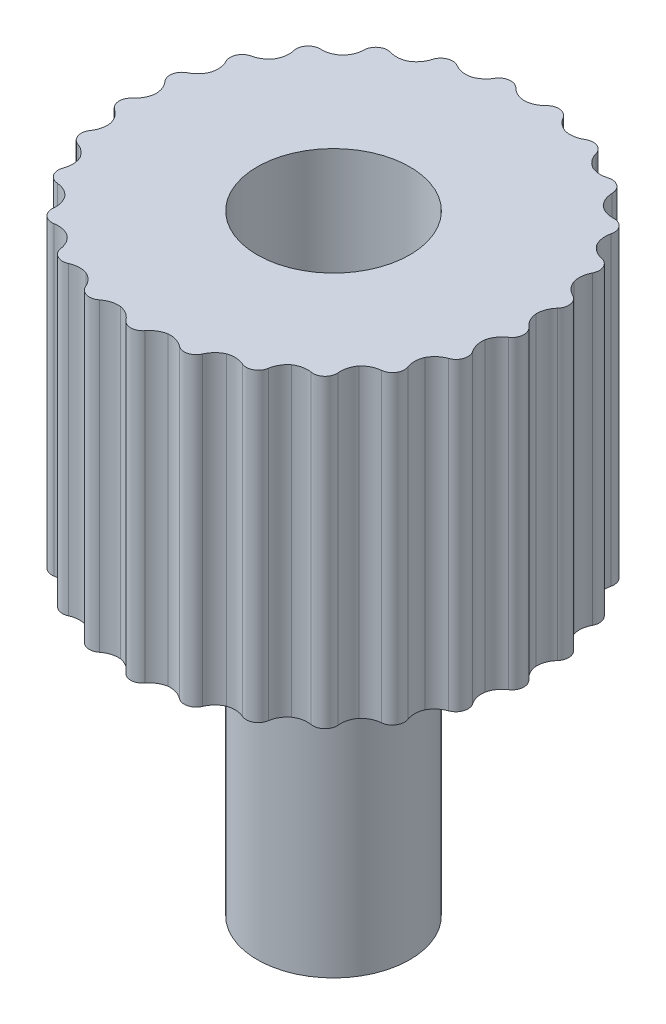
SolidWorks part; units mm, degrees
ref_plane "Front Plane" through (0, 0, 0) normal (0, 0, 1) x (1, 0, 0)
ref_plane "Top Plane" through (0, 0, 0) normal (0, 1, 0) x (1, 0, 0)
ref_plane "Right Plane" through (0, 0, 0) normal (1, 0, 0) x (0, 0, -1)
sketch "Sketch1" plane through (0, 0, 0) normal (0, 1, 0) x (1, 0, 0)
  circle A0 centre (0, 0) radius 2.5
  arc A1 (-0.157, -2.4951) -> (0.157, -2.4951) centre (0, -2.5) ccw
  arc A2 (-0.7725, -2.3776) -> (-0.4685, -2.4557) centre (-0.6217, -2.4215) ccw
  arc A3 (-1.3396, -2.1108) -> (-1.0644, -2.2621) centre (-1.2044, -2.1908) ccw
  arc A4 (-1.8224, -1.7114) -> (-1.5936, -1.9263) centre (-1.7114, -1.8224) ccw
  arc A5 (-2.1908, -1.2044) -> (-2.0225, -1.4695) centre (-2.1108, -1.3396) ccw
  arc A6 (-2.4215, -0.6217) -> (-2.3244, -0.9203) centre (-2.3776, -0.7725) ccw
  arc A7 (-2.5, 0) -> (-2.4803, -0.3133) centre (-2.4951, -0.157) ccw
  arc A8 (-2.4215, 0.6217) -> (-2.4803, 0.3133) centre (-2.4557, 0.4685) ccw
  arc A9 (-2.1908, 1.2044) -> (-2.3244, 0.9203) centre (-2.2621, 1.0644) ccw
  arc A10 (-1.8224, 1.7114) -> (-2.0225, 1.4695) centre (-1.9263, 1.5936) ccw
  arc A11 (-1.3396, 2.1108) -> (-1.5936, 1.9263) centre (-1.4695, 2.0225) ccw
  arc A12 (-0.7725, 2.3776) -> (-1.0644, 2.2621) centre (-0.9203, 2.3244) ccw
  arc A13 (-0.157, 2.4951) -> (-0.4685, 2.4557) centre (-0.3133, 2.4803) ccw
  arc A14 (0.4685, 2.4557) -> (0.157, 2.4951) centre (0.3133, 2.4803) ccw
  arc A15 (1.0644, 2.2621) -> (0.7725, 2.3776) centre (0.9203, 2.3244) ccw
  arc A16 (1.5936, 1.9263) -> (1.3396, 2.1108) centre (1.4695, 2.0225) ccw
  arc A17 (2.0225, 1.4695) -> (1.8224, 1.7114) centre (1.9263, 1.5936) ccw
  arc A18 (2.3244, 0.9203) -> (2.1908, 1.2044) centre (2.2621, 1.0644) ccw
  arc A19 (2.4803, 0.3133) -> (2.4215, 0.6217) centre (2.4557, 0.4685) ccw
  arc A20 (2.4803, -0.3133) -> (2.5, 0) centre (2.4951, -0.157) ccw
  arc A21 (2.3244, -0.9203) -> (2.4215, -0.6217) centre (2.3776, -0.7725) ccw
  arc A22 (2.0225, -1.4695) -> (2.1908, -1.2044) centre (2.1108, -1.3396) ccw
  arc A23 (1.5936, -1.9263) -> (1.8224, -1.7114) centre (1.7114, -1.8224) ccw
  arc A24 (1.0644, -2.2621) -> (1.3396, -2.1108) centre (1.2044, -2.1908) ccw
  arc A25 (0.4685, -2.4557) -> (0.7725, -2.3776) centre (0.6217, -2.4215) ccw
  circle A26 centre (0, 0) radius 1
  point P78 (0, 0)
  point P82 (0, 0)
  dimension "D1" = 5
  dimension "D2" = 7.2
  dimension "D3" = 25
extrude "Boss-Extrude1" add sketch "Sketch1" along normal blind 4 contours A0 | A0 A2 | A0 A3 | A0 A4 | A0 A5 | A0 A6 | A0 A7 | A0 A8 | A0 A9 | A0 A10 | A0 A11 | A0 A12 | A0 A13 | A0 A14 | A0 A15 | A0 A16 | A0 A17 | A0 A18 | A0 A19 | A0 A20 | A0 A21 | A0 A22 | A0 A23 | A0 A24 | A0 A25 | A0 A1 region at (2.4245, 0, 0.1525) region at (2.5607, 0, 0.1611) region at (2.5203, 0, -0.4808) region at (2.4402, 0, 0.7929) region at (2.3216, 0, -1.0924) region at (2.1663, 0, 1.3748) region at (1.977, 0, -1.6355) region at (1.7564, 0, 1.8704) region at (1.5081, 0, -2.0757) region at (1.2361, 0, 2.2484) region at (0.9445, 0, -2.3856) region at (0.6381, 0, 2.4852) region at (0.3216, 0, -2.5455) region at (0, 0, 2.5658) region at (-0.3216, 0, -2.5455) region at (-0.6381, 0, 2.4852) region at (-0.9445, 0, -2.3856) region at (-1.2361, 0, 2.2484) region at (-1.5081, 0, -2.0757) region at (-1.7564, 0, 1.8704) region at (-1.977, 0, -1.6355) region at (-2.1663, 0, 1.3748) region at (-2.3216, 0, -1.0924) region at (-2.4402, 0, 0.7929) region at (-2.5203, 0, -0.4808) region at (-2.5607, 0, 0.1611)
fillet "Fillet3" radius 0.3 50 edges at (-0.7725, 2, 2.3776) (-1.0644, 2, 2.2621) (1.8224, 2, -1.7114) (1.5936, 2, -1.9263) (-2.3244, 2, 0.9203) (-2.1908, 2, 1.2044) (-2.4215, 2, 0.6217) (-2.4803, 2, 0.3133) (-2.5, 2, 0) (-2.4803, 2, -0.3133) (-2.4215, 2, -0.6217) (-2.3244, 2, -0.9203) (-2.0225, 2, -1.4695) (-2.1908, 2, -1.2044) (-1.8224, 2, -1.7114) (-1.5936, 2, -1.9263) (-1.3396, 2, -2.1108) (-1.0644, 2, -2.2621) (-0.7725, 2, -2.3776) (-0.4685, 2, -2.4557) (0.7725, 2, -2.3776) (0.4685, 2, -2.4557) (-0.157, 2, -2.4951) (0.157, 2, -2.4951) (1.3396, 2, -2.1108) (1.0644, 2, -2.2621) (2.4215, 2, -0.6217) (2.1908, 2, -1.2044) (2.0225, 2, -1.4695) (2.3244, 2, -0.9203) (2.4803, 2, -0.3133) (2.4803, 2, 0.3133) (2.5, 2, 0) (2.4215, 2, 0.6217) (2.1908, 2, 1.2044) (2.3244, 2, 0.9203) (2.0225, 2, 1.4695) (1.8224, 2, 1.7114) (1.3396, 2, 2.1108) (1.5936, 2, 1.9263) (1.0644, 2, 2.2621) (0.7725, 2, 2.3776) (0.157, 2, 2.4951) (-1.8224, 2, 1.7114) (-1.3396, 2, 2.1108) (0.4685, 2, 2.4557) (-0.157, 2, 2.4951) (-1.5936, 2, 1.9263) (-2.0225, 2, 1.4695) (-0.4685, 2, 2.4557)
sketch "Sketch2" plane through (0, 0, 0) normal (0, -1, 0) x (1, 0, 0)
  circle A0 centre (0, 0) radius 1
  dimension "D1" = 2
extrude "Boss-Extrude2" add sketch "Sketch2" along normal blind 4
